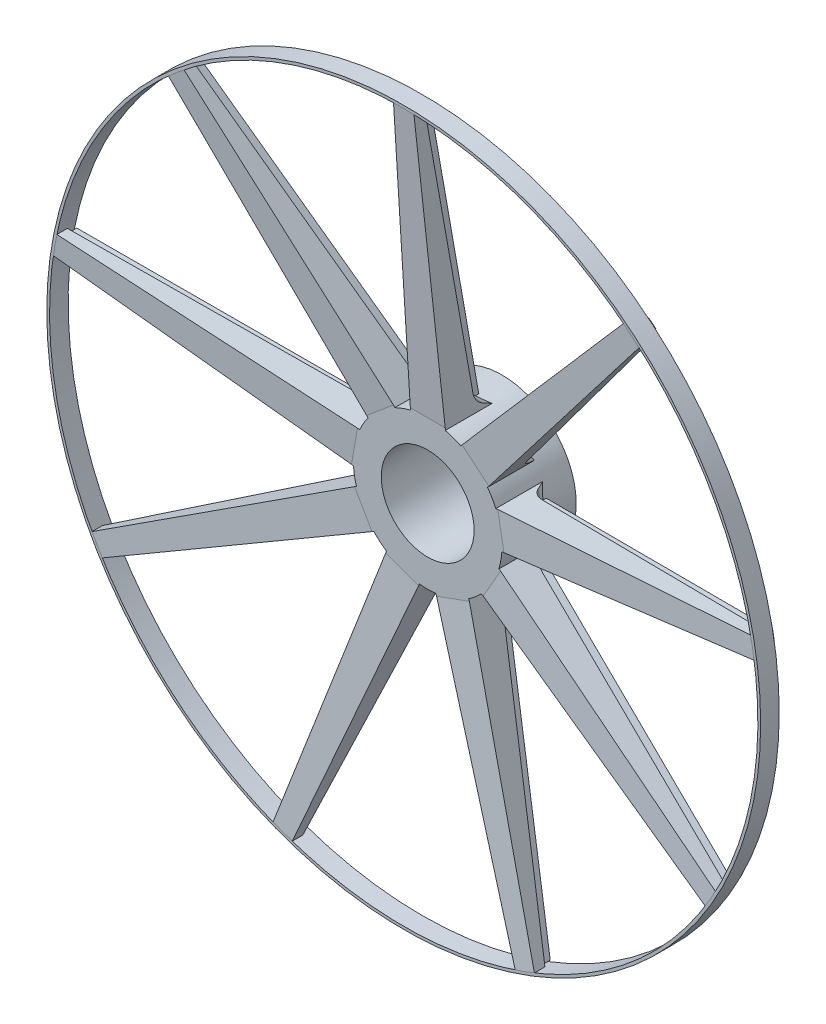
SolidWorks part; units mm, degrees
ref_plane "Front Plane" through (0, 0, 0) normal (0, 0, 1) x (1, 0, 0)
ref_plane "Top Plane" through (0, 0, 0) normal (0, 1, 0) x (1, 0, 0)
ref_plane "Right Plane" through (0, 0, 0) normal (1, 0, 0) x (0, 0, -1)
sketch "Sketch1" plane through (0, 0, 0) normal (0, 0, 1) x (1, 0, 0)
  line L0 (-20.031, 0) -> (20.031, 0) construction
  line L1 (0, 20.031) -> (0, -20.031) construction
  circle A1 centre (0, 0) radius 25
  circle A2 centre (0, 0) radius 40
  dimension "D1" = 50
  dimension "D2" = 80
extrude "Boss-Extrude1" add sketch "Sketch1" along normal blind 40
sketch "Sketch2" plane through (0, 0, 0) normal (0, 0, -1) x (-1, 0, 0)
  point P0 (0, 0)
sketch "Sketch3" plane through (0, 0, 0) normal (0, 1, 0) x (1, 0, 0)
  line L0 (0, 8.7146) -> (0, -51.2596) construction
sketch "Sketch4" plane through (0, 0, 0) normal (1, 0, 0) x (0, 0, -1)
  line L0 (-40, 40) -> (-15, 40)
  line L3 (-52.9037, 190.75) -> (-40, 40)
  line L4 (8.7146, 0) -> (-51.2596, 0) construction
  line L6 (-41.5813, 190.75) -> (-52.9037, 190.75)
  line L7 (-15, 40) -> (-41.5813, 190.75)
  dimension "D1" = 190.75
  dimension "D2" = 80
sketch "Sketch5" plane through (0, 0, 0) normal (0, 0, -1) x (-1, 0, 0)
extrude "Boss-Extrude2" add sketch "Sketch4" along normal blind 9.5 and the other way blind 9.5
sketch "Sketch6" plane through (0, 0, 40) normal (0, 0, 1) x (1, 0, 0)
  line L0 (-9.5, 40) -> (-9.5, 30.5512)
  line L1 (-9.5, 30.5512) -> (9.5, 30.5512)
  line L2 (9.5, 30.5512) -> (9.5, 40)
  line L3 (-9.5, 40) -> (9.5, 40)
  circle A0 centre (0, 0) radius 32.5
  circle M1 centre (0, 0) radius 40
extrude "Boss-Extrude3" add sketch "Sketch6" against normal blind 25 contours L3 L0 M1 | L3 L2 M1 | L1 L2 L0 M1 region at (-7.1318, 39.6575, 40) region at (7.1318, 39.6575, 40) region at (0, 31.3512, 40)
sketch "Sketch7" plane through (9.5, 0, 0) normal (1, 0, 0) x (0, 0, -1)
  line L0 (-15, 40) -> (-14.0447, 34.5825)
  line L1 (-15, 40) -> (-41.5813, 190.75) construction
  line L2 (-14.0447, 34.5825) -> (-14.7982, 38.8555)
  line L3 (-15, 38.8555) -> (-14.7982, 38.8555)
  line M2 (-15, 38.8555) -> (-15, 40)
extrude "Boss-Extrude4" add sketch "Sketch7" against normal blind 19 contours L3 L2 M2 region at (9.5, 39.237, 14.9327)
sketch "Sketch10" plane through (-9.5, 0, 0) normal (-1, 0, 0) x (0, 0, 1)
  line L0 (47.2425, 190.75) -> (24.8878, 48.7549)
  line L1 (41.5813, 190.75) -> (52.9037, 190.75) construction
  line L3 (14.7982, 38.8555) -> (19.7272, 41.4929)
  line L4 (14.7982, 38.8555) -> (41.5813, 190.75)
  line L5 (41.5813, 190.75) -> (47.2425, 190.75)
  arc A0 (24.8878, 48.7549) -> (19.7272, 41.4929) centre (15.0094, 50.31) cw
  point P5 (24.114, 43.8401)
  point P6 (24.114, 43.8401)
  dimension "D1" = 10
sketch "Sketch16" plane through (-9.5, 0, 0) normal (-1, 0, 0) x (0, 0, 1)
  line L5 (14.7982, 38.8555) -> (35.81, 38.8555) construction
  line L6 (40, 38.8555) -> (14.7982, 38.8555) construction
  line L7 (27.2417, 38.8555) -> (26.4088, 28.3283)
extrude "Cut-Extrude3" cut sketch "Sketch10" against normal blind 7
mirror "Mirror1" about plane through (0, 0, 0) normal (1, 0, 0) of "Cut-Extrude3"
sketch "Sketch18" plane through (0, -2.6442, 16.7958) normal (0, 0.1555, -0.9878) x (-1, 0, 0)
  line L0 (-2.5, 195.7762) -> (-5.5, 195.7762)
  line L2 (2.5, 195.7762) -> (5.5, 195.7762)
  line L3 (2.5, 195.7762) -> (9.5, 195.7762) construction
  line L4 (-2.5, 195.7762) -> (-9.5, 195.7762) construction
sketch3d "3DSketch1" plane through (0, 0, 0) normal (0, 0, 1) x (1, 0, 0)
sketch "Sketch20" plane through (0, 0, 0) normal (0, 0, -1) x (-1, 0, 0)
  line L0 (5.5, 190.75) -> (9.5, 33.5919)
  line L1 (9.5, 38.8555) -> (9.5, 28.3283) construction
  line L2 (9.5, 33.5919) -> (9.5, 190.75)
  line L3 (9.5, 190.75) -> (5.5, 190.75)
  line L4 (-5.5, 190.75) -> (-9.5, 38.8555)
  line L5 (-9.5, 38.8555) -> (-9.5, 190.75)
  line L6 (-9.5, 190.75) -> (-5.5, 190.75)
extrude "Cut-Extrude6" cut sketch "Sketch20" against normal through all
pattern_circular "CirPattern11" count 9 over 360 about axis through (0, 0, 0) along (0, 0, 1) of bodies 112
ref_plane "Plane1" through (0, 0, 52.9037) normal (0, 0, -1) x (-1, 0, 0)
sketch "Sketch21" plane through (0, 0, 52.9037) normal (0, 0, -1) x (-1, 0, 0)
  circle A0 centre (0, 0) radius 190.75
  circle A1 centre (0, 0) radius 192.25
  dimension "D1" = 384.5
  dimension "D2" = 381.5
extrude "Boss-Extrude5" add sketch "Sketch21" along normal blind 10
